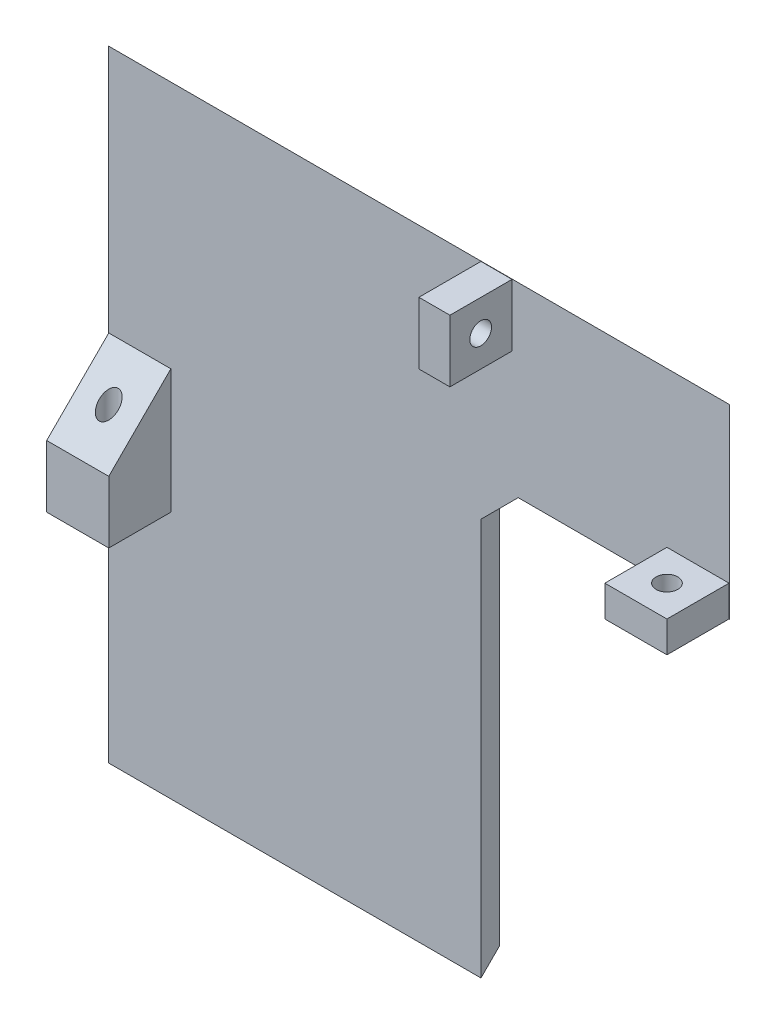
SolidWorks part; units mm, degrees
ref_plane "Plan de face" through (0, 0, 0) normal (0, 0, 1) x (1, 0, 0)
ref_plane "Plan de dessus" through (0, 0, 0) normal (0, 1, 0) x (1, 0, 0)
ref_plane "Plan de droite" through (0, 0, 0) normal (1, 0, 0) x (0, 0, -1)
sketch "Esquisse1" plane through (0, 0, 0) normal (0, 0, 1) x (1, 0, 0)
  line L1 (0, 100) -> (100, 100)
  line L2 (0, 100) -> (0, 0)
  line L3 (0, 0) -> (100, 0)
  line L4 (100, 100) -> (100, 0)
  dimension "D1" = 100
  dimension "D2" = 100
extrude "Boss.-Extru.1" add sketch "Esquisse1" along normal blind 3
sketch "Esquisse2" plane through (0, 0, 3) normal (0, 0, 1) x (1, 0, 0)
  line L0 (0, 100) -> (0, 0) construction
  line L1 (0.05, 60) -> (10.05, 60)
  line L2 (0.05, 60) -> (0.05, 40)
  line L3 (0.05, 40) -> (10.05, 40)
  line L4 (10.05, 60) -> (10.05, 40)
  line L5 (100, 100) -> (0, 100) construction
  line L6 (89.95, 60) -> (99.95, 60)
  line L7 (89.95, 60) -> (89.95, 40)
  line L8 (89.95, 40) -> (99.95, 40)
  line L9 (99.95, 60) -> (99.95, 40)
  line L10 (100, 0) -> (100, 100) construction
  dimension "D1" = 0.05
  dimension "D2" = 10
  dimension "D3" = 40
  dimension "D4" = 20
  dimension "D5" = 20
  dimension "D6" = 10
  dimension "D7" = 0.05
  dimension "D8" = 40
extrude "Boss.-Extru.2" add sketch "Esquisse2" along normal blind 10
chamfer "Chanfrein1" distance 10 angle 45 2 edges at (94.95, 60, 13) (5.05, 60, 13)
sketch "Esquisse3" plane through (0, 40, 0) normal (0, -1, 0) x (1, 0, 0)
  line L0 (10.05, 13) -> (10.05, 3) construction
  line L1 (0.05, 13) -> (10.05, 13) construction
  line L2 (99.95, 13) -> (99.95, 3) construction
  line L3 (89.95, 13) -> (99.95, 13) construction
  circle A0 centre (5.0462, 8) radius 1.525
  circle A1 centre (94.95, 8) radius 1.525
  dimension "D1" = 3.05
  dimension "D2" = 5.0038
  dimension "D3" = 5
  dimension "D4" = 3.05
  dimension "D5" = 5
  dimension "D6" = 5
extrude "Enlèv. mat.-Extru.1" cut sketch "Esquisse3" against normal through all
chamfer "Chanfrein2" distance 3 angle 45 4 edges at (50, 0, 0) (100, 50, 0) (50, 100, 0) (0, 50, 0)
sketch "Esquisse4" plane through (0, 0, 3) normal (0, 0, 1) x (1, 0, 0)
  line L0 (100, 100) -> (0, 100) construction
  line L1 (65, 99.95) -> (60, 99.95)
  line L2 (65, 99.95) -> (65, 89.95)
  line L3 (65, 89.95) -> (60, 89.95)
  line L4 (60, 99.95) -> (60, 89.95)
  line L5 (100, 0) -> (100, 100) construction
  dimension "D1" = 5
  dimension "D2" = 10
  dimension "D3" = 0.05
  dimension "D4" = 40
extrude "Boss.-Extru.3" add sketch "Esquisse4" along normal blind 10
sketch "Esquisse5" plane through (65, 0, 0) normal (1, 0, 0) x (0, 0, -1)
  line L0 (-3, 89.95) -> (-3, 99.95) construction
  line L1 (-13, 99.95) -> (-3, 99.95) construction
  circle A0 centre (-8.05, 94.95) radius 1.75
  dimension "D1" = 3.5
  dimension "D2" = 5.05
  dimension "D3" = 5
extrude "Enlèv. mat.-Extru.2" cut sketch "Esquisse5" against normal blind 10 contours A0
sketch "Esquisse6" plane through (0, 0, 3) normal (0, 0, 1) x (1, 0, 0)
  line L0 (100, 0) -> (100, 100) construction
  line L1 (115.203, -6.3999) -> (60, -6.3999)
  line L2 (115.203, -6.3999) -> (115.203, 70)
  line L3 (115.203, 70) -> (60, 70)
  line L4 (60, -6.3999) -> (60, 70)
  line L5 (0, 0) -> (100, 0) construction
  dimension "D1" = 40
  dimension "D2" = 70
extrude "Enlèv. mat.-Extru.3" cut sketch "Esquisse6" against normal blind 10
sketch "Esquisse9" plane through (0, 0, 3) normal (0, 0, 1) x (1, 0, 0)
  line L1 (89.95, 75.05) -> (99.95, 75.05)
  line L2 (89.95, 75.05) -> (89.95, 70.05)
  line L3 (89.95, 70.05) -> (99.95, 70.05)
  line L4 (99.95, 75.05) -> (99.95, 70.05)
  line L6 (100, 70) -> (100, 100) construction
  line L7 (100, 70) -> (60, 70) construction
  dimension "D1" = 5
  dimension "D2" = 10
  dimension "D3" = 0.05
  dimension "D4" = 0.05
extrude "Boss.-Extru.5" add sketch "Esquisse9" along normal blind 10
sketch "Esquisse10" plane through (0, 70, 0) normal (0, -1, 0) x (1, 0, 0)
  line L0 (89.95, 13) -> (89.95, 3) construction
  line L1 (89.95, 13) -> (99.95, 13) construction
  circle A0 centre (94.95, 8) radius 1.75
  dimension "D1" = 5
  dimension "D2" = 5
  dimension "D3" = 3.5
extrude "Enlèv. mat.-Extru.5" cut sketch "Esquisse10" against normal blind 10
chamfer "Chanfrein3" distance 6 angle 45 1 edges at (60, 70, 1.5)
